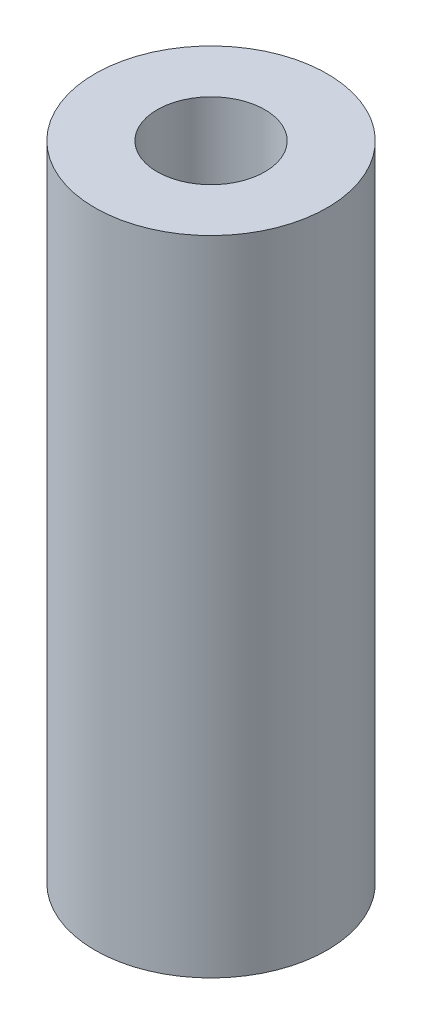
SolidWorks part; units mm, degrees
ref_plane "Front Plane" through (0, 0, 0) normal (0, 0, 1) x (1, 0, 0)
ref_plane "Top Plane" through (0, 0, 0) normal (0, 1, 0) x (1, 0, 0)
ref_plane "Right Plane" through (0, 0, 0) normal (1, 0, 0) x (0, 0, -1)
sketch "Sketch1" plane through (0, 0, 0) normal (0, 1, 0) x (1, 0, 0)
  circle A0 centre (0, 0) radius 3.45
  circle A1 centre (0, 0) radius 1.6
extrude "Boss-Extrude2" add sketch "Sketch1" along normal blind 19.1
